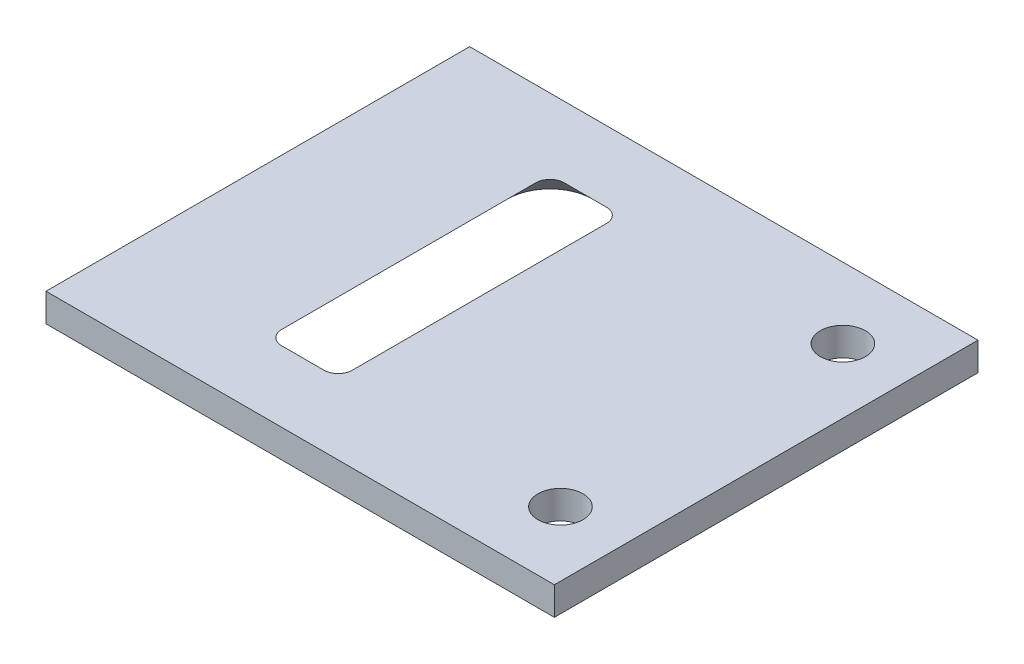
SolidWorks part; units mm, degrees
material "6061-T4 (SS)"
ref_plane "Front Plane" through (0, 0, 0) normal (0, 0, 1) x (1, 0, 0)
ref_plane "Top Plane" through (0, 0, 0) normal (0, 1, 0) x (1, 0, 0)
ref_plane "Right Plane" through (0, 0, 0) normal (1, 0, 0) x (0, 0, -1)
sketch "Sketch2" plane through (0, 0, 0) normal (0, 1, 0) x (1, 0, 0)
  line L5 (-13.189, 15) -> (22.811, 15)
  line L6 (-13.189, 15) -> (-13.189, -15)
  line L7 (-13.189, -15) -> (22.811, -15)
  line L8 (22.811, 15) -> (22.811, -15)
  line L9 (-13.189, 15) -> (22.811, -15) construction
  line L10 (-13.189, -15) -> (22.811, 15) construction
  dimension "D1" = 36
  dimension "D2" = 30
extrude "Boss-Extrude1" add sketch "Sketch2" along normal blind 2
sketch "Sketch4" plane through (0, 2, 0) normal (0, 1, 0) x (1, 0, 0)
  line L1 (1.5, -10) -> (-1.5, -10)
  line L2 (2.5, -9) -> (2.5, 9)
  line L3 (1.5, 10) -> (-1.5, 10)
  line L4 (-2.5, -9) -> (-2.5, 9)
  line L5 (2.5, -10) -> (-2.5, 10) construction
  line L6 (2.5, 10) -> (-2.5, -10) construction
  arc A0 (1.5, -10) -> (2.5, -9) centre (1.5, -9) ccw
  arc A1 (2.5, 9) -> (1.5, 10) centre (1.5, 9) ccw
  arc A2 (-1.5, 10) -> (-2.5, 9) centre (-1.5, 9) ccw
  arc A3 (-1.5, -10) -> (-2.5, -9) centre (-1.5, -9) cw
  point P0 (0, 0)
  dimension "D3" = 1
  dimension "D1" = 20
  dimension "D2" = 5
extrude "Cut-Extrude4" cut sketch "Sketch4" against normal through all draft 45 draft outward yes
sketch "Sketch5" plane through (0, 2, 0) normal (0, 1, 0) x (1, 0, 0)
  line L0 (18.2427, -15) -> (18.2427, 15) construction
  line L1 (-13.189, -15) -> (22.811, -15) construction
  line L2 (22.811, 15) -> (-13.189, 15) construction
  circle A0 centre (18.2427, -10) radius 1.595
  circle A1 centre (18.2427, 10) radius 1.595
  dimension "D3" = 3.19
  dimension "D4" = 3.19
  dimension "D1" = 5
  dimension "D2" = 5
extrude "Cut-Extrude5" cut sketch "Sketch5" against normal through all
